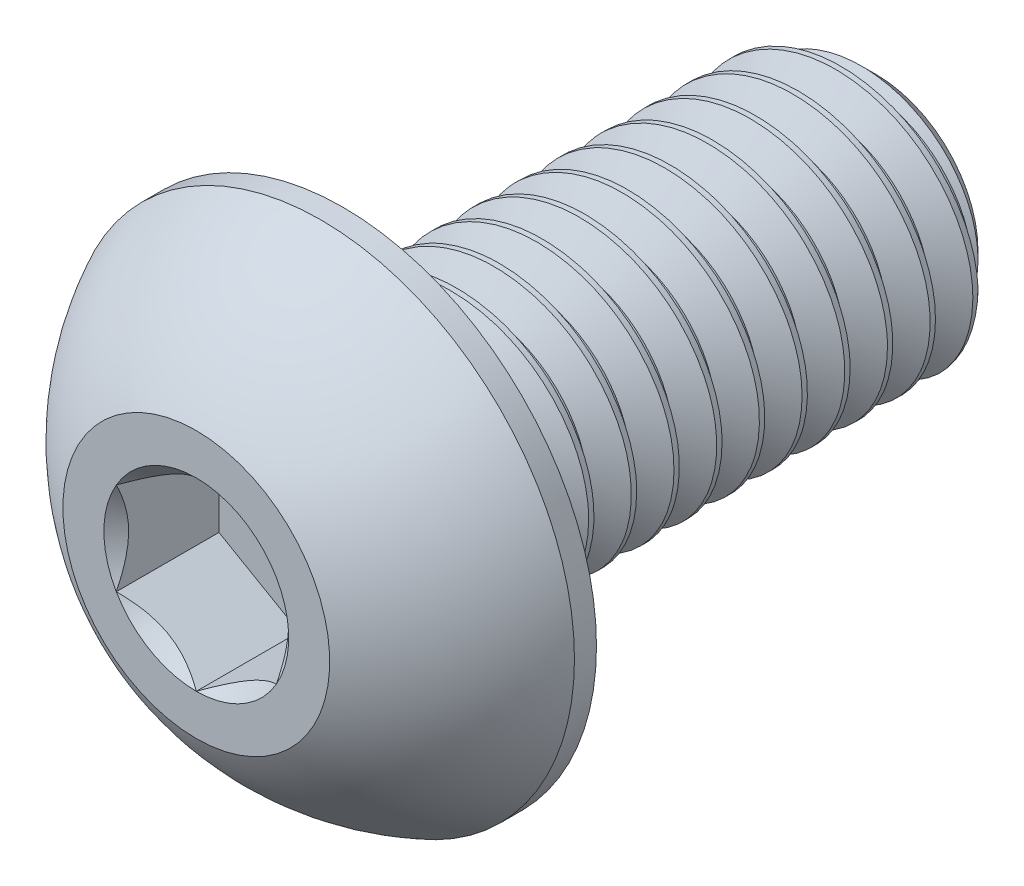
SolidWorks part; units mm, degrees
ref_plane "Front" through (0, 0, 0) normal (0, 0, 1) x (1, 0, 0)
ref_plane "Top" through (0, 0, 0) normal (0, 1, 0) x (1, 0, 0)
ref_plane "Right" through (0, 0, 0) normal (1, 0, 0) x (0, 0, -1)
sketch "Sketch1" plane through (0, 0, 0) normal (1, 0, 0) x (0, 0, -1)
  line L2 (2.75, 2.5) -> (12.75, 2.5)
  line L3 (12.75, 2.5) -> (12.75, 0)
  line L4 (12.75, 0) -> (2.75, 0)
  line L6 (2.3375, 4.75) -> (2.75, 4.75) construction
  line L7 (12.75, 2.5) -> (12.75, -2.5) construction
  line L8 (0, 0) -> (2.75, 0) construction
  line L9 (2.75, 4.75) -> (2.75, -4.75) construction
  line L11 (2.75, 2.5) -> (2.75, 0)
  line L13 (0, 1.5) -> (0, -1.5) construction
  line L14 (0, 1.5) -> (0, 2.5) construction
  arc A3 (0, 2.5) -> (2.3375, 4.75) centre (4.6581, 0) cw construction
  dimension "D1" = 0.4125
revolve "Revolve1" add sketch "Sketch1" angle 360 mid plane about L4
sketch "Sketch3" plane through (0, 0, -12.75) normal (0, 0, -1) x (-1, 0, 0)
  circle A0 centre (0, 0) radius 2.5
curve "Helix/Spiral1" pitch 0.8 height 10.8 radius 2.5 centre (0, 0, -12.75) axis (0, 0, 1) start towards (0, 1, 0)
sketch "Sketch2" plane through (0, 0, 0) normal (1, 0, 0) x (0, 0, -1)
  line L0 (12.75, 2.5) -> (13.45, 2.5)
  line L1 (13.45, 2.5) -> (13.15, 1.9804)
  line L2 (13.15, 1.9804) -> (13.05, 1.9804)
  line L3 (13.05, 1.9804) -> (12.75, 2.5)
  line L4 (12.9, 2.2402) -> (13.3, 2.2402) construction
  dimension "D1" = 60
  dimension "D2" = 0.1
  dimension "D3" = 0.4
chamfer "Chamfer1" distance 0.6 angle 45 1 edges at (0, 2.5, -12.75)
sweep "Cut-Sweep1" cut profiles "Sketch2" path "Helix/Spiral1" align with end faces yes
sketch "Sketch7" plane through (0, 0, 0) normal (1, 0, 0) x (0, 0, -1)
  line L6 (2.3375, 4.75) -> (2.75, 4.75) construction
  line L8 (0, 0) -> (2.75, 0) construction
  line L11 (2.75, 4.75) -> (2.75, -4.75) construction
  line L12 (2.3375, 4.75) -> (2.75, 4.75)
  line L13 (0, 0) -> (2.75, 0)
  line L14 (0, 1.5) -> (0, -1.5) construction
  line L15 (2.75, 4.75) -> (2.75, 0)
  line L16 (0, 2.5) -> (0, 0)
  arc A2 (2.3375, 4.75) -> (0, 2.5) centre (4.6581, 0) ccw construction
  arc A3 (2.3375, 4.75) -> (0, 2.5) centre (4.6581, 0) ccw
revolve "Revolve2" add sketch "Sketch7" angle 360 mid plane about L13
sketch "Sketch5" plane through (0, 0, 0) normal (0, 0, 1) x (1, 0, 0)
  line L1 (1.5, -0.866) -> (1.5, 0.866)
  line L2 (1.5, 0.866) -> (0, 1.7321)
  line L3 (0, 1.7321) -> (-1.5, 0.866)
  line L4 (-1.5, 0.866) -> (-1.5, -0.866)
  line L5 (-1.5, -0.866) -> (0, -1.7321)
  line L6 (0, -1.7321) -> (1.5, -0.866)
  circle A0 centre (0, 0) radius 1.5 construction
extrude "Cut-Extrude2" cut sketch "Sketch5" against normal blind 1.925
sketch "Sketch6" plane through (0, 0, 0) normal (0, 0, 1) x (1, 0, 0)
  circle A0 centre (0, 0) radius 1.7321
extrude "Cut-Extrude3" cut sketch "Sketch6" against normal blind 1.925 draft 45
sketch "Sketch9" [suppressed] plane through (0, 0, -2.75) normal (0, 0, 1) x (1, 0, 0)
  circle A2 centre (0, 0) radius 2.5
extrude "Boss-Extrude2" [suppressed] add sketch "Sketch9" against normal offset from surface (13 mm away) 20 up to face at (0, 1.9, -12.75)
sketch "Sketch10" plane through (0, 0, 0) normal (1, 0, 0) x (0, 0, -1)
  line L0 (12.75, 2.5) -> (12.75, -2.5) construction
  point P0 (11.55, -2.5)
  dimension "D1" = 1.2
equation "\"D3@Helix/Spiral1\" = \"Lg@Sketch1\" + \"D4@Helix/Spiral1\""
equation "\"D2@Sketch2\" = \"D4@Helix/Spiral1\" * .125"
equation "\"D3@Sketch2\" = \"D4@Helix/Spiral1\" * .5"
equation "\"D1@Chamfer1\" = \"D4@Helix/Spiral1\" * .75"
equation "\"D1@Cut-Extrude2\" = \"Head Ht@Sketch1\" * .7"
equation "\"D1@Sketch1\" = \"Head Ht@Sketch1\" * .15"
equation "\"D1@Sketch10\" = \"D4@Helix/Spiral1\" * 1.5"
equation "\"D1@Cut-Extrude3\" = \"D1@Cut-Extrude2\""
